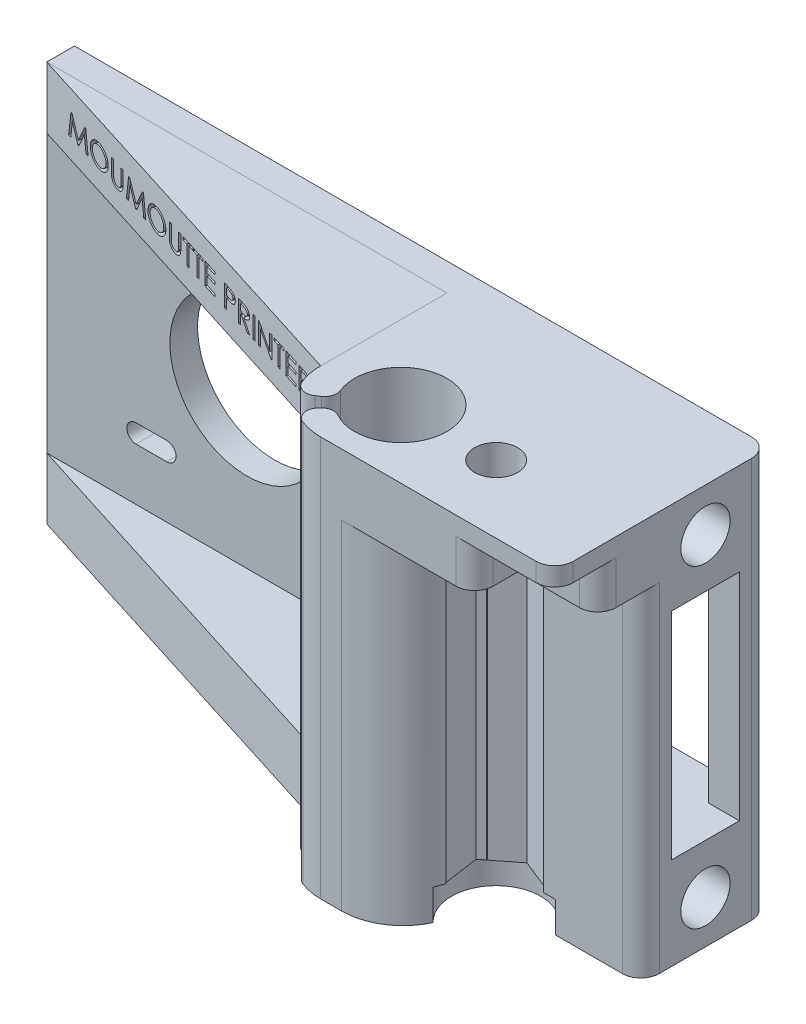
SolidWorks part; units mm, degrees
ref_plane "Front Plane" through (0, 0, 0) normal (0, 0, 1) x (1, 0, 0)
ref_plane "Top Plane" through (0, 0, 0) normal (0, 1, 0) x (1, 0, 0)
ref_plane "Right Plane" through (0, 0, 0) normal (1, 0, 0) x (0, 0, -1)
sketch "Sketch1" plane through (0, 0, 0) normal (0, 1, 0) x (1, 0, 0)
  line L1 (0, 0) -> (48, 0)
  line L2 (0, 0) -> (0, 35)
  line L3 (0, 35) -> (48, 35)
  line L4 (48, 0) -> (48, 35)
  dimension "D1" = 48
  dimension "D2" = 35
extrude "Boss-Extrude1" add sketch "Sketch1" along normal blind 65
sketch "Sketch2" plane through (0, 65, 0) normal (0, 1, 0) x (1, 0, 0)
  line L0 (0, 0) -> (48, 0) construction
  line L1 (0, 35) -> (0, 0) construction
  circle A0 centre (12, 11) radius 7.5
  circle A1 centre (27.5, 11) radius 3.5
  dimension "D1" = 15
  dimension "D5" = 7
  dimension "D6" = 15.5
  dimension "D2" = 11
  dimension "D3" = 12
  dimension "D4" = 11
extrude "Cut-Extrude1" cut sketch "Sketch2" against normal through all
sketch "Sketch3" plane through (48, 0, 0) normal (1, 0, 0) x (0, 0, -1)
  line L0 (0, 65) -> (35, 65) construction
  line L1 (0, 0) -> (14, 0)
  line L2 (0, 0) -> (0, 55)
  line L3 (0, 55) -> (14, 55)
  line L4 (14, 0) -> (14, 55)
  dimension "D1" = 21
  dimension "D2" = 10
extrude "Cut-Extrude2" cut sketch "Sketch3" against normal blind 25
sketch "Sketch4" plane through (48, 0, 0) normal (1, 0, 0) x (0, 0, -1)
  line L0 (14, 0) -> (14, 55) construction
  line L1 (19, 50) -> (30, 50)
  line L2 (19, 50) -> (19, 15)
  line L3 (19, 15) -> (30, 15)
  line L4 (30, 50) -> (30, 15)
  line L5 (35, 65) -> (35, 0) construction
  line L6 (14, 0) -> (35, 0) construction
  line L7 (0, 65) -> (35, 65) construction
  dimension "D1" = 5
  dimension "D2" = 5
  dimension "D3" = 15
  dimension "D4" = 15
extrude "Cut-Extrude3" cut sketch "Sketch4" against normal through all
sketch "Sketch7" plane through (48, 0, 0) normal (1, 0, 0) x (0, 0, -1)
  line L0 (14, 0) -> (35, 0) construction
  line L1 (0, 65) -> (35, 65) construction
  line L2 (35, 65) -> (35, 0) construction
  circle A0 centre (24.5, 58) radius 4
  circle A1 centre (24.5, 7) radius 4
  dimension "D1" = 8
  dimension "D2" = 8
  dimension "D3" = 7
  dimension "D4" = 7
  dimension "D5" = 10.5
  dimension "D6" = 10.5
extrude "Cut-Extrude4" cut sketch "Sketch7" against normal blind 28.5
sketch "Sketch8" plane through (0, 0, -35) normal (0, 0, -1) x (-1, 0, 0)
  line L0 (-48, 65) -> (0, 65) construction
  line L1 (-5, 15) -> (-43, 15)
  line L2 (-5, 15) -> (-5, 50)
  line L3 (-5, 50) -> (-43, 50)
  line L4 (-43, 15) -> (-43, 50)
  line L5 (-48, 0) -> (0, 0) construction
  line L6 (0, 65) -> (0, 0) construction
  line L7 (-48, 65) -> (-48, 0) construction
  dimension "D1" = 15
  dimension "D2" = 15
  dimension "D3" = 5
  dimension "D4" = 5
extrude "Cut-Extrude5" cut sketch "Sketch8" against normal blind 10
sketch "Sketch9" plane through (48, 0, 0) normal (1, 0, 0) x (0, 0, -1)
  line L1 (0, 55) -> (7, 55)
  line L2 (0, 55) -> (0, 62)
  line L3 (0, 62) -> (7, 62)
  line L4 (7, 55) -> (7, 62)
  dimension "D1" = 7
  dimension "D2" = 7
extrude "Cut-Extrude7" cut sketch "Sketch9" against normal blind 13
fillet "Fillet2" radius 3 5 edges at (48, 63.5, 0) (35, 58.5, 0) (48, 58.5, -7) (48, 27.5, -14) (48, 32.5, -35)
sketch "Sketch10" plane through (0, 0, 0) normal (0, -1, 0) x (1, 0, 0)
  line L1 (26.6708, -16.8303) -> (32.1346, -14.6333)
  line L2 (32.1346, -14.6333) -> (32.9638, -8.803)
  line L3 (32.9638, -8.803) -> (28.3292, -5.1697)
  line L4 (28.3292, -5.1697) -> (22.8654, -7.3667)
  line L5 (22.8654, -7.3667) -> (22.0362, -13.197)
  line L6 (22.0362, -13.197) -> (26.6708, -16.8303)
  circle A0 centre (27.5, -11) radius 5.1 construction
  dimension "D1" = 10.2
extrude "Cut-Extrude8" cut sketch "Sketch10" against normal blind 60
sketch "Sketch11" plane through (0, 0, 0) normal (0, -1, 0) x (1, 0, 0)
  circle A0 centre (27.5, -11) radius 7.25
  dimension "D1" = 14.5
extrude "Cut-Extrude9" cut sketch "Sketch11" against normal blind 5
fillet "Fillet3" radius 10 2 edges at (23, 27.5, 0) (0, 32.5, 0)
sketch "Sketch12" plane through (0, 65, 0) normal (0, 1, 0) x (1, 0, 0)
  line L0 (1.92, 4.1081) -> (5.8088, 6.7669)
  line L2 (4.0312, 1.9767) -> (7.0354, 5.3784)
  line L3 (7.0354, 5.3784) -> (5.8088, 6.7669)
  line L5 (1.92, 4.1081) -> (1.6822, 3.8703)
  line L6 (1.6822, 3.8703) -> (3.8414, 1.7112)
  line L7 (3.8414, 1.7112) -> (4.0312, 1.9767)
  circle A0 centre (12, 11) radius 7.5 construction
  arc A1 (0, 10) -> (10, 0) centre (10, 10) ccw construction
  dimension "D1" = 3
extrude "Cut-Extrude11" cut sketch "Sketch12" against normal through all
fillet "Fillet4" radius 2 4 edges at (7.0354, 32.5, -5.3784) (5.8088, 32.5, -6.7669) (4.0312, 32.5, -1.9767) (1.92, 32.5, -4.1081)
sketch "Sketch14" plane through (0, 0, -35) normal (0, 0, -1) x (-1, 0, 0)
  line L1 (0, 0) -> (65, 0)
  line L2 (0, 0) -> (0, 65)
  line L3 (0, 65) -> (65, 65)
  line L4 (65, 0) -> (65, 65)
  dimension "D1" = 65
  dimension "D2" = 65
extrude "Boss-Extrude2" add sketch "Sketch14" against normal blind 4.5
sketch "Sketch15" plane through (0, 65, 0) normal (0, 1, 0) x (1, 0, 0)
  line L0 (-65, 30.5) -> (0, 30.5)
  line L1 (0, 30.5) -> (0, 10)
  line L2 (0, 10) -> (-65, 30.5)
extrude "Boss-Extrude3" add sketch "Sketch15" against normal blind 10 separate body
sketch "Sketch16" plane through (0, 0, 0) normal (0, -1, 0) x (1, 0, 0)
  line L0 (-65, -30.5) -> (0, -30.5)
  line L1 (0, -30.5) -> (0, -10)
  line L2 (0, -10) -> (-65, -30.5)
extrude "Boss-Extrude4" add sketch "Sketch16" against normal blind 10
sketch "Sketch17" plane through (0, 0, -30.5) normal (0, 0, 1) x (1, 0, 0)
  line L0 (-19.5, 51) -> (-14.5, 51) construction
  line L1 (-45.5, 20) -> (-50.5, 20) construction
  line L2 (-45.5, 18.5) -> (-50.5, 18.5)
  line L3 (-45.5, 21.5) -> (-50.5, 21.5)
  line L4 (-19.5, 20) -> (-14.5, 20) construction
  line L5 (-19.5, 21.5) -> (-14.5, 21.5)
  line L6 (-19.5, 18.5) -> (-14.5, 18.5)
  line L7 (-65, 10) -> (0, 10) construction
  line L8 (-50.5, 51) -> (-45.5, 51) construction
  line L9 (-50.5, 52.5) -> (-45.5, 52.5)
  line L10 (-50.5, 49.5) -> (-45.5, 49.5)
  line L11 (-19.5, 52.5) -> (-14.5, 52.5)
  line L12 (-19.5, 49.5) -> (-14.5, 49.5)
  line L15 (0, 65) -> (0, 10) construction
  arc A0 (-50.5, 52.5) -> (-50.5, 49.5) centre (-50.5, 51) ccw
  arc A1 (-45.5, 49.5) -> (-45.5, 52.5) centre (-45.5, 51) ccw
  arc A2 (-19.5, 21.5) -> (-19.5, 18.5) centre (-19.5, 20) ccw
  arc A3 (-14.5, 18.5) -> (-14.5, 21.5) centre (-14.5, 20) ccw
  arc A4 (-45.5, 18.5) -> (-45.5, 21.5) centre (-45.5, 20) ccw
  arc A5 (-50.5, 21.5) -> (-50.5, 18.5) centre (-50.5, 20) ccw
  arc A6 (-19.5, 52.5) -> (-19.5, 49.5) centre (-19.5, 51) ccw
  arc A7 (-14.5, 49.5) -> (-14.5, 52.5) centre (-14.5, 51) ccw
  circle A8 centre (-32.5, 35.5) radius 12.5
  point P2 (-48, 51)
  point P7 (-17, 20)
  point P10 (-48, 20)
  point P25 (-17, 51)
  dimension "D2" = 31
  dimension "D3" = 3
  dimension "D4" = 5
  dimension "D16" = 25
  dimension "D5" = 3
  dimension "D6" = 5
  dimension "D7" = 5
  dimension "D8" = 10
  dimension "D9" = 31
  dimension "D10" = 3
  dimension "D11" = 3
  dimension "D12" = 5
  dimension "D13" = 31
  dimension "D14" = 31
  dimension "D15" = 32.5
  dimension "D17" = 15.5
  dimension "D18" = 15.5
extrude "Cut-Extrude12" cut sketch "Sketch17" against normal through all
sketch "Sketch18" plane through (2.8685, 0, -9.0953) normal (-0.3008, 0, 0.9537) x (0.9537, 0, 0.3008)
  text T0 "<b>MOUMOUTTE PRINTER</b>" font "Century Gothic" height 3.5
extrude "Cut-Extrude13" cut sketch "Sketch18" against normal blind 2
